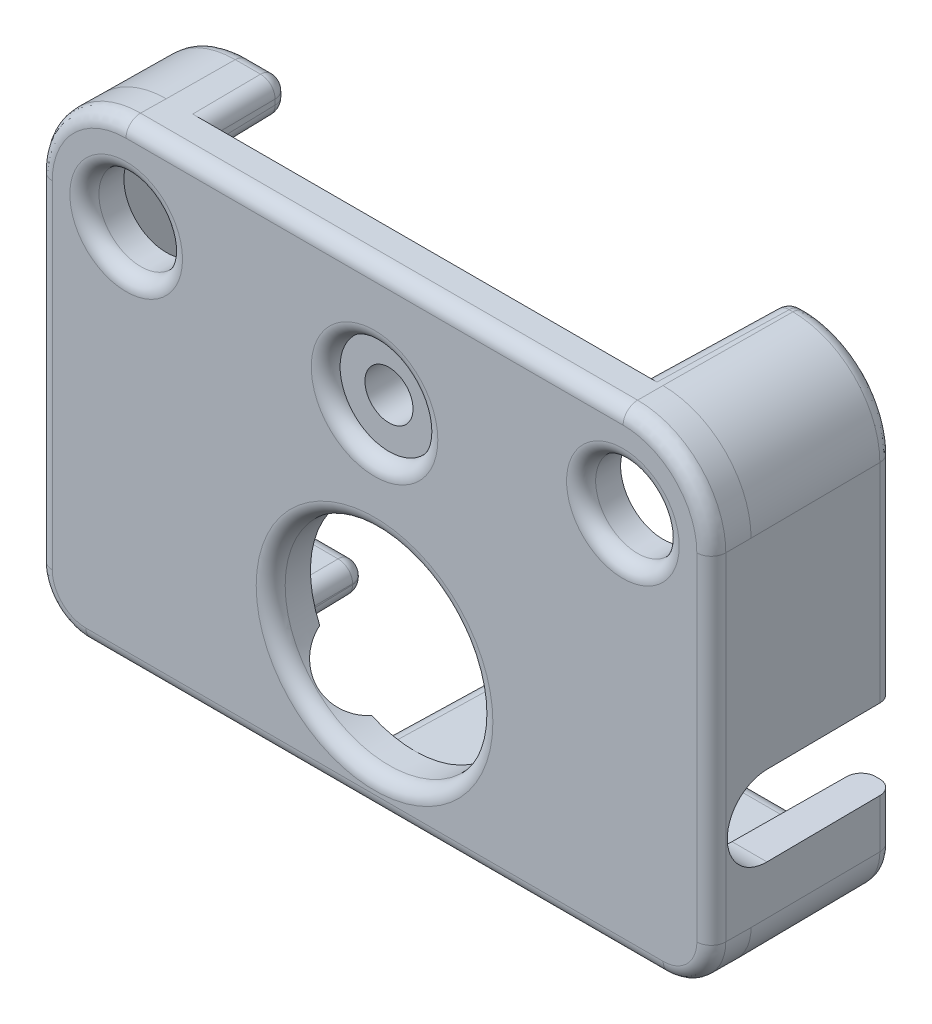
SolidWorks part; units mm, degrees
material "Acrylic (Medium-high impact)"
ref_plane "Front Plane" through (0, 0, 0) normal (0, 0, 1) x (1, 0, 0)
ref_plane "Top Plane" through (0, 0, 0) normal (0, 1, 0) x (1, 0, 0)
ref_plane "Right Plane" through (0, 0, 0) normal (1, 0, 0) x (0, 0, -1)
sketch "Sketch1" plane through (0, 0, 0) normal (0, 0, 1) x (1, 0, 0)
  line L1 (21, -21) -> (-21, -21)
  line L2 (21, -21) -> (21, 21)
  line L3 (21, 21) -> (-21, 21)
  line L4 (-21, -21) -> (-21, 21)
  line L5 (21, -21) -> (-21, 21) construction
  line L6 (21, 21) -> (-21, -21) construction
  circle A0 centre (0, 0) radius 6.5
  point P0 (0, 0)
  dimension "D3" = 13
  dimension "D1" = 42
  dimension "D2" = 42
extrude "Boss-Extrude1" add sketch "Sketch1" along normal blind 2.5 draft 0.5 draft outward yes
sketch "Sketch3" plane through (0, 0, 2.5) normal (0, 0, 1) x (1, 0, 0)
  line L1 (-30.6074, -8.5) -> (32.2688, -8.5)
  line L2 (-30.6074, -8.5) -> (-30.6074, -30.3417)
  line L3 (-30.6074, -30.3417) -> (32.2688, -30.3417)
  line L4 (32.2688, -8.5) -> (32.2688, -30.3417)
  dimension "D1" = 8.5
extrude "Cut-Extrude2" cut sketch "Sketch3" against normal through all draft 1
sketch "Sketch4" plane through (0, 0, 2.5) normal (0, 0, 1) x (1, 0, 0)
  circle A0 centre (-15.5, 15.5) radius 3.15
  circle A2 centre (-15.5, 15.5) radius 1.6782
  circle A4 centre (15.5, 15.5) radius 1.6782
  circle A5 centre (15.5, 15.5) radius 3.15
  dimension "D1" = 6.3
sketch "Sketch5" plane through (0, 0, 0) normal (0, 1, 0) x (1, 0, 0)
  line L0 (0, 0) -> (0, -11.8875) construction
fillet "Fillet1" radius 5.5 2 edges at (21.0109, 21.0109, 1.25) (-21.0109, 21.0109, 1.25)
fillet "Fillet2" radius 3 2 edges at (-21.0109, -8.5218, 1.25) (21.0109, -8.5218, 1.25)
sketch "Sketch17" plane through (0, 0, 0) normal (0, 0, -1) x (-1, 0, 0)
  line L4 (-17.9994, -8.5436) -> (17.9994, -8.5436)
  line L5 (21, -5.5427) -> (21, 15.5002)
  line L6 (15.5002, 21) -> (-15.5002, 21)
  line L7 (-21, 15.5002) -> (-21, -5.5427)
  line L8 (-17.9994, -8.5436) -> (17.9994, -8.5436)
  line L9 (21, -5.5427) -> (21, 15.5002)
  line L10 (15.5002, 21) -> (-15.5002, 21)
  line L11 (-21, 15.5002) -> (-21, -5.5427)
  line L20 (-17.8, -6.5436) -> (17.8, -6.5436)
  line L21 (18.8, -5.5436) -> (18.8, 15.5)
  line L22 (15.5, 18.8) -> (-15.5, 18.8)
  line L23 (-18.8, 15.5) -> (-18.8, -5.5436)
  arc A2 (18.8, 15.5) -> (15.5, 18.8) centre (15.5, 15.5) ccw
  arc A3 (-15.5, 18.8) -> (-18.8, 15.5) centre (-15.5, 15.5) ccw
  arc A4 (-17.8, -6.5436) -> (-18.8, -5.5436) centre (-17.8, -5.5436) cw
  arc A5 (17.8, -6.5436) -> (18.8, -5.5436) centre (17.8, -5.5436) ccw
  ellipse E4 centre (17.9999, -5.5432) end of major axis (16.6581, -8.227) minor radius 3 (17.9994, -8.5436) -> (21, -5.5427) ccw
  ellipse E5 centre (15.4998, 15.4998) end of major axis (19.3892, 19.3892) minor radius 5.5 (21, 15.5002) -> (15.5002, 21) ccw
  ellipse E6 centre (-15.4998, 15.4998) end of major axis (-11.6104, 11.6104) minor radius 5.5 (-15.5002, 21) -> (-21, 15.5002) ccw
  ellipse E7 centre (-17.9999, -5.5432) end of major axis (-19.3417, -2.8593) minor radius 3 (-21, -5.5427) -> (-17.9994, -8.5436) ccw
  ellipse E8 centre (17.9999, -5.5432) end of major axis (16.6581, -8.227) minor radius 3 (17.9994, -8.5436) -> (21, -5.5427) ccw
  ellipse E9 centre (15.4998, 15.4998) end of major axis (11.6104, 11.6104) minor radius 5.5 (21, 15.5002) -> (15.5002, 21) ccw
  ellipse E10 centre (-15.4998, 15.4998) end of major axis (-11.6104, 11.6104) minor radius 5.5 (-15.5002, 21) -> (-21, 15.5002) ccw
  ellipse E11 centre (-17.9999, -5.5432) end of major axis (-16.6581, -8.227) minor radius 3 (-21, -5.5427) -> (-17.9994, -8.5436) ccw
  dimension "D2" = 3.3
  dimension "D4" = 1
  dimension "D3" = 2
  dimension "D1" = 0
extrude "Boss-Extrude3" add sketch "Sketch17" along normal blind 9 draft 0.5
sketch "Sketch23" plane through (0, 0, 0) normal (0, 0, -1) x (-1, 0, 0)
  line L1 (2.0856, -2.2991) -> (11.8453, -2.2991)
  line L2 (2.0856, -2.2991) -> (2.0856, -11.2394)
  line L3 (2.0856, -11.2394) -> (11.8453, -11.2394)
  line L4 (11.8453, -2.2991) -> (11.8453, -11.2394)
extrude "Cut-Extrude11" cut sketch "Sketch23" along normal through all draft 1 draft outward yes
sketch "Sketch24" plane through (0, 0, 2.5) normal (0, 0, 1) x (1, 0, 0)
  line L0 (0, 13.5353) -> (0, 0) construction
  circle A0 centre (0, 13.5353) radius 1.5
  dimension "D1" = 3
  dimension "D2" = 13.5353
extrude "Cut-Extrude12" cut sketch "Sketch24" against normal through all
sketch "Sketch18" plane through (0, 0, 0) normal (0, 0, -1) x (-1, 0, 0)
  line L1 (-14.2255, 22.2919) -> (12.9494, 22.2919)
  line L2 (-14.2255, 22.2919) -> (-14.2255, 18.3583)
  line L3 (-14.2255, 18.3583) -> (12.9494, 18.3583)
  line L4 (12.9494, 22.2919) -> (12.9494, 18.3583)
extrude "Cut-Extrude6" cut sketch "Sketch18" along normal through all draft 1 draft outward yes
ref_plane "Plane1" through (0, 0, -5.2) normal (0, 0, -1) x (-1, 0, 0)
sketch "Sketch19" plane through (0, 0, -5.2) normal (0, 0, -1) x (-1, 0, 0)
  line L1 (11.4144, 25.5715) -> (27.4733, 25.5715)
  line L2 (11.4144, 25.5715) -> (11.4144, 8.6191)
  line L3 (11.4144, 8.6191) -> (27.4733, 8.6191)
  line L4 (27.4733, 25.5715) -> (27.4733, 8.6191)
extrude "Cut-Extrude13" cut sketch "Sketch19" along normal up to next (3.8 mm away) draft 1 draft outward yes
fillet "Fillet9" radius 0.9 46 edges at (14.9413, 18.8785, -9) (17.889, 17.889, -9) (18.8785, 4.9782, -9) (18.5626, -6.3063, -9) (7.9357, -6.6222, -9) (-1.9285, -7.5436, -9) (8.0354, -8.4651, -9) (20.2818, -7.3672, -9) (20.9215, 4.9787, -9) (18.8847, 19.7349, -9) (14.9414, 20.9215, -9) (14.3826, 19.9, -9) (-19.8234, -7.8257, -9) (-15.0009, -8.4651, -9) (-12.0024, -7.5436, -9) (-14.9012, -6.6222, -9) (-18.5626, -6.3063, -9) (-20.9215, 1.505, -9) (-18.8785, 1.5046, -9) (6.4782, 0, 2.5) (-19.411, 19.411, 2.5) (0, 21.0218, 2.5) (19.411, 19.411, 2.5) (21.0218, 5.0115, 2.5) (20.1429, -7.621, 2.5) (0, -8.5, 2.5) (-20.1429, -7.621, 2.5) (-21.0218, 5.0115, 2.5) (-19.9, 8.5528, -9) (-18.9054, 19.7609, -5.2) (-14.2701, 18.8454, -5.2) (-17.8655, 17.8655, -5.2) (14.304, 20.9607, -4.5) (14.304, 18.8393, -4.5) (-12.9947, 18.8227, -2.6) (-12.9947, 20.9773, -2.6) (-13.0401, 19.9, -5.2) (-18.8454, 12.0596, -5.2) (-18.862, 8.586, -7.1) (-20.938, 8.586, -7.1) (-11.9239, -6.5829, -4.5) (-11.9239, -8.5044, -4.5) (-2.0071, -6.5829, -4.5) (-2.0071, -8.5044, -4.5)
sketch "Sketch25" plane through (0, 0, 0) normal (1, 0, 0) x (0, 0, -1)
  line L0 (-2.5, -5.5149) -> (-2.5, 15.5141) construction
  line L3 (0, 0) -> (1, 0) construction
  circle A0 centre (1, 0) radius 2.5
  dimension "D2" = 5
  dimension "D1" = 3.5
extrude "Cut-Extrude14" cut sketch "Sketch25" along normal through all
pattern_circular "CirPattern1" count 2 every 135 of "Cut-Extrude14"
sketch "Sketch27" plane through (0, 0, 0) normal (1, 0, 0) x (0, 0, -1)
  line L0 (1, 0) -> (1, 2.5) construction
  line L1 (1, 0) -> (1, -2.5) construction
  circle A1 centre (1, 0) radius 2.5
  circle A2 centre (1, 0) radius 2.5
  dimension "D1" = 0
ref_plane "Plane2" through (0, 0, -1) normal (0, 0, -1) x (-1, 0, 0)
sketch "Sketch28" plane through (0, 0, -1) normal (0, 0, -1) x (-1, 0, 0)
  line L0 (0, 2.5) -> (0, -2.5) construction
  line L1 (0, 2.5) -> (-25.5502, 2.5)
  line L2 (0, 2.5) -> (0, -2.5)
  line L3 (0, -2.5) -> (-25.5502, -2.5)
  line L4 (-25.5502, 2.5) -> (-25.5502, -2.5)
  line L5 (0, 0) -> (0, 2.5) construction
  line L6 (0, 0) -> (0, -2.5) construction
extrude "Cut-Extrude15" cut sketch "Sketch28" along normal through all
sketch "Sketch29" plane through (0, 0, 2.5) normal (0, 0, 1) x (1, 0, 0)
  circle A0 centre (-15.5, 15.3353) radius 2.6
  circle A1 centre (15.5, 15.3353) radius 2.6
  dimension "D1" = 5.2
extrude "Cut-Extrude16" cut sketch "Sketch29" against normal through all draft 1 draft outward yes
fillet "Fillet10" radius 0.9 2 edges at (18.1, 15.3353, 2.5) (-12.9, 15.3353, 2.5)
ref_plane "Plane3" through (0, 8, 0) normal (0, 1, 0) x (1, 0, 0)
sketch "Sketch30" plane through (0, 8, 0) normal (0, 1, 0) x (1, 0, 0)
  line L0 (9.2127, 1.2) -> (11.1661, 1.2) construction
  line L1 (12.4564, -0.9853) -> (5.969, -0.9853)
  line L2 (15.1255, 0) -> (-13.8494, 0) construction
  arc A0 (12.4564, -0.9853) -> (5.969, -0.9853) centre (9.2127, -2.3) ccw
  dimension "D2" = 3.5
  dimension "D1" = 1.2
extrude "Boss-Extrude4" add sketch "Sketch30" along normal blind 9.7
fillet "Fillet11" radius 2 2 edges at (9.2127, 17.7, -1.2) (9.2127, 8, -1.2)
sketch "Sketch32" plane through (0, 0, 0) normal (0, 0, -1) x (-1, 0, 0)
  circle A0 centre (0, 13.5353) radius 2.5
  circle A1 centre (0, 13.5353) radius 1.5 construction
  circle A2 centre (0, 13.5353) radius 1.5
  dimension "D1" = 5
extrude "Boss-Extrude5" add sketch "Sketch32" along normal blind 0.6
sketch "Sketch33" plane through (0, 0, 2.5) normal (0, 0, 1) x (1, 0, 0)
  circle A0 centre (0, 13.5353) radius 3.05
  dimension "D1" = 6.1
extrude "Cut-Extrude17" cut sketch "Sketch33" against normal blind 0.9
fillet "Fillet12" radius 0.9 1 edges at (3.05, 13.5353, 2.5)
